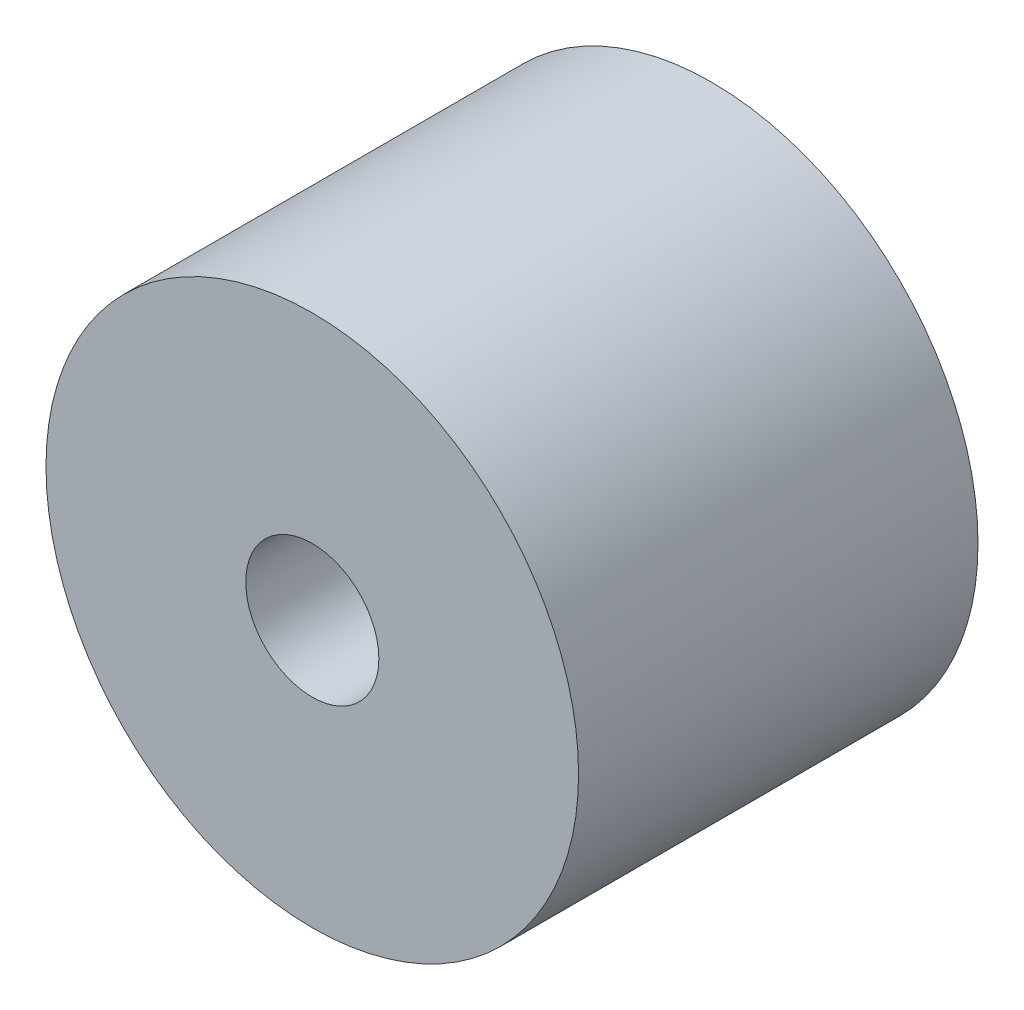
SolidWorks part; units mm, degrees
ref_plane "前视基准面" through (0, 0, 0) normal (0, 0, 1) x (1, 0, 0)
ref_plane "上视基准面" through (0, 0, 0) normal (0, 1, 0) x (1, 0, 0)
ref_plane "右视基准面" through (0, 0, 0) normal (1, 0, 0) x (0, 0, -1)
other "Configuration Table"
sketch "Sketch1" plane through (0, 0, 0) normal (0, 0, 1) x (1, 0, 0)
  circle A0 centre (0, 0) radius 100
extrude "Boss-Extrude1" add sketch "Sketch1" along normal blind 150
ref_plane "Plane1" through (0, 0, 150) normal (0, 0, 1) x (1, 0, 0)
sketch "Sketch2" plane through (0, 0, 150) normal (0, 0, 1) x (1, 0, 0)
  circle A0 centre (0, 0) radius 25
extrude "Cut-Extrude1" cut sketch "Sketch2" against normal blind 50
ref_plane "bottom_face" through (0, 0, 0) normal (0, 0, 1) x (1, 0, 0)
ref_plane "top_mount_face" through (0, 0, 150) normal (0, 0, 1) x (1, 0, 0)
sketch3d "3DSketch1"
  line L0 (0, 0, 0) -> (0, 0, 150) construction
ref_axis "center_axis_z" through (0, 0, 0) along (0, 0, 1)
